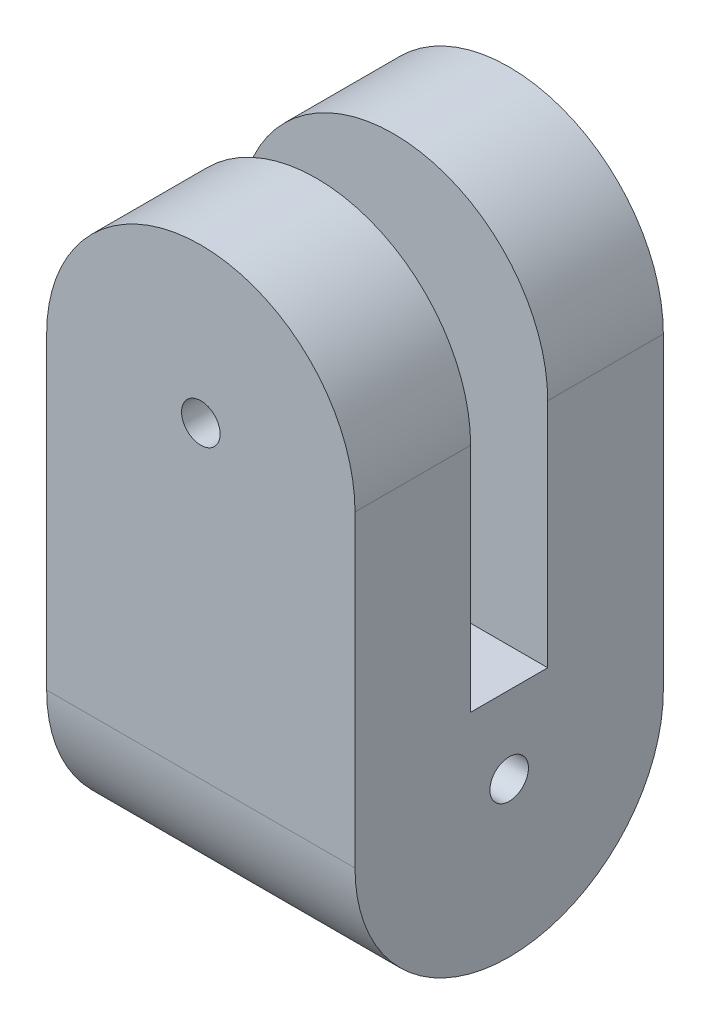
SolidWorks part; units mm, degrees
material "1060 Alloy"
ref_plane "Front Plane" through (0, 0, 0) normal (0, 0, 1) x (1, 0, 0)
ref_plane "Top Plane" through (0, 0, 0) normal (0, 1, 0) x (1, 0, 0)
ref_plane "Right Plane" through (0, 0, 0) normal (1, 0, 0) x (0, 0, -1)
sketch "Sketch3" plane through (0, 0, 0) normal (0, 0, 1) x (1, 0, 0)
  line L1 (0, 0) -> (20, 0)
  line L2 (0, 0) -> (0, 20)
  line L4 (20, 0) -> (20, 20)
  arc A0 (20, 20) -> (0, 20) centre (10, 20) ccw
  dimension "D1" = 20
  dimension "D2" = 20
extrude "Boss-Extrude2" add sketch "Sketch3" along normal blind 20 contours A0 L2 L1 L4
sketch "Sketch4" plane through (20, 0, 0) normal (1, 0, 0) x (0, 0, -1)
  line L0 (0, 30) -> (-20, 30) construction
  line L1 (-12.5, 30) -> (-7.5, 30)
  line L2 (-12.5, 30) -> (-12.5, 5)
  line L3 (-12.5, 5) -> (-7.5, 5)
  line L4 (-7.5, 30) -> (-7.5, 5)
  line L5 (0, 20) -> (0, 30) construction
  point P6 (-10, 30)
  dimension "D1" = 25
  dimension "D2" = 5
  dimension "D3" = 10
extrude "Cut-Extrude2" cut sketch "Sketch4" against normal through all both and the other way through all
sketch "Sketch5" plane through (0, 0, 0) normal (0, 0, -1) x (-1, 0, 0)
  circle A0 centre (-10, 20) radius 1.25
  arc A1 (0, 20) -> (-20, 20) centre (-10, 20) ccw construction
  dimension "D1" = 2.5
extrude "Cut-Extrude3" cut sketch "Sketch5" against normal through all both and the other way through all
sketch "Sketch6" plane through (20, 0, 0) normal (1, 0, 0) x (0, 0, -1)
  line L0 (-20, 0) -> (0, 0) construction
  line L1 (-20, 0) -> (0, 0)
  arc A0 (-20, 0) -> (0, 0) centre (-10, 0) ccw
extrude "Boss-Extrude3" add sketch "Sketch6" against normal blind 20
sketch "Sketch7" plane through (20, 0, 0) normal (1, 0, 0) x (0, 0, -1)
  circle A0 centre (-10, 0) radius 1.25
  arc A1 (-20, 0) -> (0, 0) centre (-10, 0) ccw construction
  dimension "D1" = 2.5
extrude "Cut-Extrude4" cut sketch "Sketch7" against normal through all both and the other way through all
ref_axis "Axis1" through (10, 20, 13.693) along (0, 0, -1)
ref_plane "Plane1" through (0, 0, 10) normal (0, 0, 1) x (1, 0, 0)
ref_point "Point1"
ref_point "Point2"
